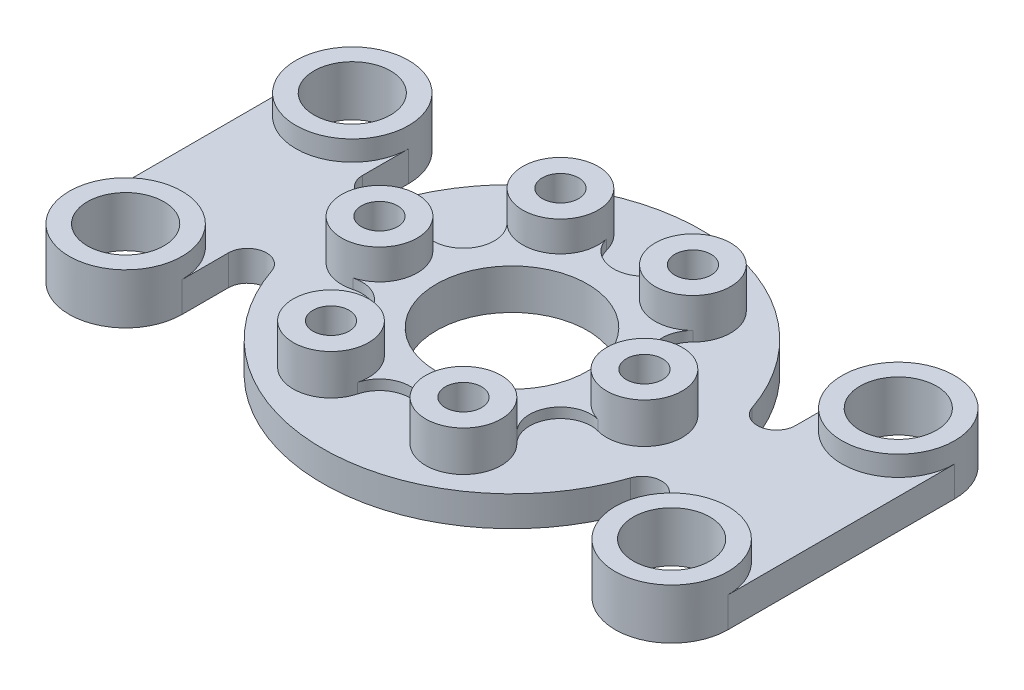
SolidWorks part; units mm, degrees
material "6061-T6 (SS)"
ref_plane "Front Plane" through (0, 0, 0) normal (0, 0, 1) x (1, 0, 0)
ref_plane "Top Plane" through (0, 0, 0) normal (0, 1, 0) x (1, 0, 0)
ref_plane "Right Plane" through (0, 0, 0) normal (1, 0, 0) x (0, 0, -1)
sketch "Sketch1" plane through (0, 0, 0) normal (0, 1, 0) x (1, 0, 0)
  line L0 (0, -55) -> (0, 55) construction
  line L1 (-215, 112.5) -> (-215, 66.5808)
  line L2 (215, -66.5808) -> (215, -112.5)
  line L3 (327, -112.5) -> (327, 112.5)
  line L4 (215, 112.5) -> (215, 66.5808)
  line L5 (-327, -112.5) -> (-327, 112.5)
  line L6 (-215, -66.5808) -> (-215, -112.5)
  circle A4 centre (-271, -112.5) radius 56
  arc A5 (-178.0097, -60.4695) -> (178.0097, -60.4695) centre (0, 0) ccw
  arc A6 (178.0097, -60.4695) -> (215, -66.5808) centre (196, -66.5808) cw
  circle A7 centre (271, -112.5) radius 38
  circle A8 centre (271, 112.5) radius 38
  arc A9 (215, 66.5808) -> (178.0097, 60.4695) centre (196, 66.5808) cw
  arc A10 (178.0097, 60.4695) -> (-178.0097, 60.4695) centre (0, 0) ccw
  circle A11 centre (-271, 112.5) radius 56
  circle A12 centre (271, 112.5) radius 56
  circle A13 centre (271, -112.5) radius 56
  arc A14 (-215, 66.5808) -> (-178.0097, 60.4695) centre (-196, 66.5808) ccw
  circle A15 centre (-271, 112.5) radius 38
  circle A16 centre (-271, -112.5) radius 38
  arc A17 (-178.0097, -60.4695) -> (-215, -66.5808) centre (-196, -66.5808) ccw
  circle A18 centre (0, 0) radius 131.5 construction
  circle A19 centre (131.5, 0) radius 37.5
  circle A20 centre (131.5, 0) radius 18
  arc A21 (125.9863, -37.679) -> (95.6241, -90.2678) centre (113.8823, -65.75) ccw
  circle A22 centre (65.75, -113.8823) radius 18
  circle A23 centre (65.75, -113.8823) radius 37.5
  circle A24 centre (-65.75, -113.8823) radius 18
  circle A25 centre (-65.75, -113.8823) radius 37.5
  circle A26 centre (-131.5, 0) radius 18
  circle A27 centre (-131.5, 0) radius 37.5
  circle A28 centre (-65.75, 113.8823) radius 18
  circle A29 centre (-65.75, 113.8823) radius 37.5
  circle A30 centre (65.75, 113.8823) radius 18
  circle A31 centre (65.75, 113.8823) radius 37.5
  arc A32 (30.3622, -127.9468) -> (-30.3622, -127.9468) centre (0, -131.5) ccw
  arc A33 (-95.6241, -90.2678) -> (-125.9863, -37.679) centre (-113.8823, -65.75) ccw
  arc A34 (-125.9863, 37.679) -> (-95.6241, 90.2678) centre (-113.8823, 65.75) ccw
  arc A35 (-30.3622, 127.9468) -> (30.3622, 127.9468) centre (0, 131.5) ccw
  arc A36 (95.6241, 90.2678) -> (125.9863, 37.679) centre (113.8823, 65.75) ccw
  circle A37 centre (0, 0) radius 75
  dimension "D1" = 19
  dimension "D2" = 188
  dimension "D3" = 76
  dimension "D6" = 112
  dimension "D7" = 112.5
  dimension "D8" = 75
  dimension "D9" = 36
  dimension "D10" = 263
  dimension "D13" = 150
  dimension "D4" = 225
  dimension "D5" = 271
  dimension "D11" = 6
  dimension "D12" = 6
extrude "Boss-Extrude1" add sketch "Sketch1" along normal blind 30 contours A17 A5 A6 L2 A13 L3 A12 L4 A9 A10 A14 L1 A11 L5 A4 L6 A31 A36 A19 A21 A23 A32 A25 A33 A27 A34 A29 A35 region at (-215.7544, 0, -89.5404)
extrude "Boss-Extrude2" add sketch "Sketch1<3>" along normal blind 50 contours A11 A15 | A4 A16 | A13 A7 | A12 A8 region at (-271, 0, -58.0839) region at (-271, 0, 58.0839) region at (271, 0, -166.9161) region at (271, 0, 166.9161)
sketch "Sketch1<3>" plane through (0, 0, 0) normal (0, 1, 0) x (1, 0, 0) same geometry as "Sketch1"
extrude "Boss-Extrude3" add sketch "Sketch1<4>" along normal blind 40 contours A36 A31 A35 A29 A34 A27 A33 A25 A32 A23 A21 A19 A37 region at (90.5297, 0, 0)
sketch "Sketch1<4>" plane through (0, 0, 0) normal (0, 1, 0) x (1, 0, 0) same geometry as "Sketch1"
extrude "Boss-Extrude4" add sketch "Sketch1<5>" along normal blind 70 contours A31 A30 | A19 A20 | A23 A22 | A25 A24 | A27 A26 | A29 A28 region at (153.6829, 0, 28.9093) region at (47.5303, 0, -82.3249) region at (99.4156, 0, 99.9376) region at (-29.6224, 0, -118.6386) region at (-83.9697, 0, 145.4397) region at (-102.5907, 0, -22.1829)
sketch "Sketch1<5>" plane through (0, 0, 0) normal (0, 1, 0) x (1, 0, 0) same geometry as "Sketch1"
